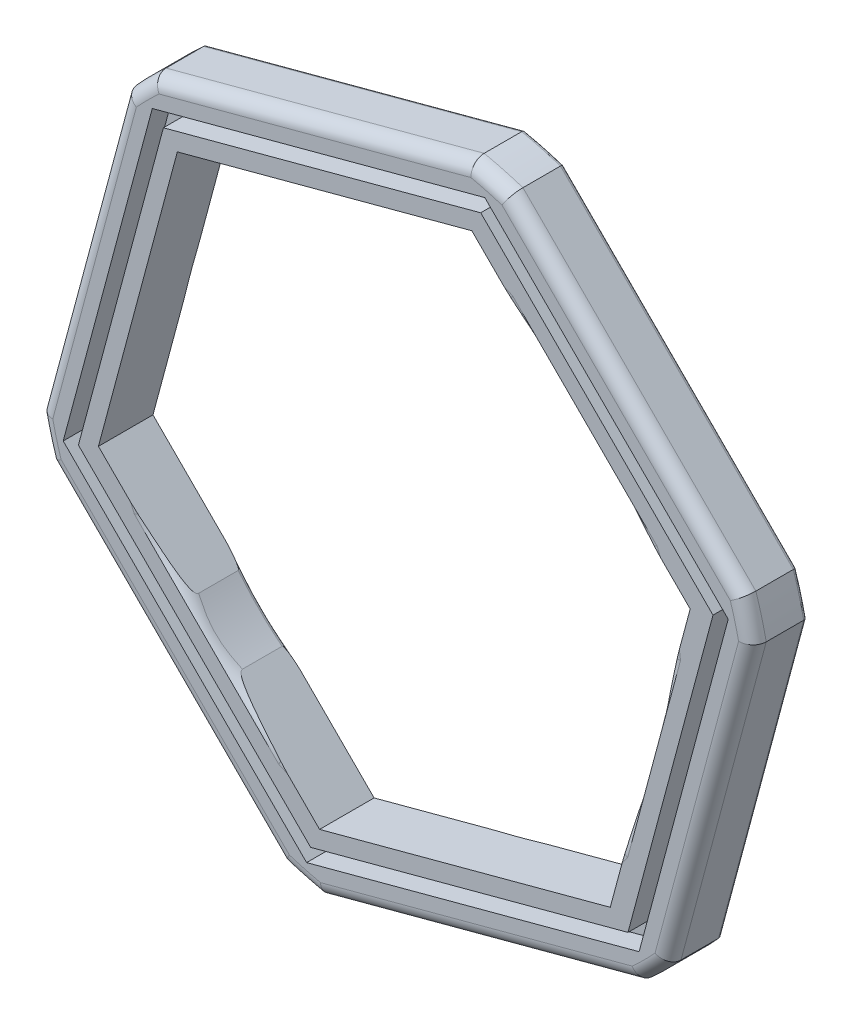
SolidWorks part; units mm, degrees
ref_plane "Спереди" through (0, 0, 0) normal (0, 0, 1) x (1, 0, 0)
ref_plane "Сверху" through (0, 0, 0) normal (0, 1, 0) x (1, 0, 0)
ref_plane "Справа" through (0, 0, 0) normal (1, 0, 0) x (0, 0, -1)
sketch "Эскиз1" plane through (0, 0, 0) normal (0, 0, 1) x (1, 0, 0)
  circle A1 centre (0, 0) radius 53.5
  circle A5 centre (0, 0) radius 39
extrude "Бобышка-Вытянуть1" add sketch "Эскиз1" along normal blind 65
sketch "Эскиз2" plane through (0, 0, 65) normal (0, 0, 1) x (1, 0, 0)
  line L0 (0, 0) -> (-8, 8) construction
  line L1 (-8, 8) -> (-59.1146, 59.1146) construction
  line L2 (-34.0759, 34.0759) -> (-46.5485, -12.4726)
  line L3 (-35.7089, 35.7089) -> (-48.7793, -13.0704)
  line L4 (-48.7793, -13.0704) -> (-13.0704, -48.7793)
  line L5 (-13.0704, -48.7793) -> (35.7089, -35.7089)
  line L6 (35.7089, -35.7089) -> (48.7793, 13.0704)
  line L7 (48.7793, 13.0704) -> (13.0704, 48.7793)
  line L8 (13.0704, 48.7793) -> (-35.7089, 35.7089)
  line L9 (-46.5485, -12.4726) -> (-12.4726, -46.5485)
  line L10 (-12.4726, -46.5485) -> (34.0759, -34.0759)
  line L11 (34.0759, -34.0759) -> (46.5485, 12.4726)
  line L12 (46.5485, 12.4726) -> (12.4726, 46.5485)
  line L13 (12.4726, 46.5485) -> (-34.0759, 34.0759)
  circle A0 centre (0, 0) radius 43.7343 construction
  dimension "D1" = 101
  dimension "D2" = 2
extrude "Вырез-Вытянуть1" cut sketch "Эскиз2" against normal blind 3
sketch "Эскиз3" plane through (0, 0, 65) normal (0, 0, 1) x (1, 0, 0)
  line L0 (43.7602, 11.7255) -> (11.7255, 43.7602)
  line L1 (11.7255, 43.7602) -> (-32.0347, 32.0347)
  line L2 (-32.0347, 32.0347) -> (-43.7602, -11.7255)
  line L3 (-43.7602, -11.7255) -> (-11.7255, -43.7602)
  line L4 (-11.7255, -43.7602) -> (32.0347, -32.0347)
  line L5 (32.0347, -32.0347) -> (43.7602, 11.7255)
  line L6 (46.5485, 12.4726) -> (12.4726, 46.5485)
  line L7 (12.4726, 46.5485) -> (-34.0759, 34.0759)
  line L8 (-34.0759, 34.0759) -> (-46.5485, -12.4726)
  line L9 (-46.5485, -12.4726) -> (-12.4726, -46.5485)
  line L10 (-12.4726, -46.5485) -> (34.0759, -34.0759)
  line L11 (34.0759, -34.0759) -> (46.5485, 12.4726)
  line L12 (46.5485, 12.4726) -> (12.4726, 46.5485)
  line L13 (12.4726, 46.5485) -> (-34.0759, 34.0759)
  line L14 (-34.0759, 34.0759) -> (-46.5485, -12.4726)
  line L15 (-46.5485, -12.4726) -> (-12.4726, -46.5485)
  line L16 (-12.4726, -46.5485) -> (34.0759, -34.0759)
  line L17 (34.0759, -34.0759) -> (46.5485, 12.4726)
  dimension "D1" = 0
  dimension "D2" = 2.5
extrude "Бобышка-Вытянуть2" add sketch "Эскиз3" along normal blind 3
fillet "Скругление2" radius 3 1 edges at (39, 0, 65)
sketch "Эскиз4" plane through (0, 0, 65) normal (0, 0, 1) x (1, 0, 0)
  line L12 (14.2658, 53.2407) -> (-38.9749, 38.9749)
  line L13 (53.2407, 14.2658) -> (14.2658, 53.2407)
  line L14 (38.9749, -38.9749) -> (53.2407, 14.2658)
  line L15 (-14.2658, -53.2407) -> (38.9749, -38.9749)
  line L16 (-53.2407, -14.2658) -> (-14.2658, -53.2407)
  line L17 (-38.9749, 38.9749) -> (-53.2407, -14.2658)
  line L18 (14.2658, 53.2407) -> (-38.9749, 38.9749)
  line L19 (53.2407, 14.2658) -> (14.2658, 53.2407)
  line L20 (38.9749, -38.9749) -> (53.2407, 14.2658)
  line L21 (-14.2658, -53.2407) -> (38.9749, -38.9749)
  line L22 (-53.2407, -14.2658) -> (-14.2658, -53.2407)
  line L23 (-38.9749, 38.9749) -> (-53.2407, -14.2658)
  circle A2 centre (0, 0) radius 58.5
  circle A3 centre (0, 0) radius 58.5
  dimension "D1" = 4
  dimension "D2" = 5
extrude "Вырез-Вытянуть2" cut sketch "Эскиз4" against normal blind 105 contours L18 L23 L22 L21 L20 L19 | A3
fillet "Скругление3" radius 2 12 edges at (13.8468, 51.677, 65) (-12.3545, 46.1078, 65) (-37.8302, 37.8302, 65) (-46.1078, 12.3545, 65) (-51.677, -13.8468, 65) (-33.7532, -33.7532, 65) (-13.8468, -51.677, 65) (37.8302, -37.8302, 65) (12.3545, -46.1078, 65) (33.7532, 33.7532, 65) (51.677, 13.8468, 65) (46.1078, -12.3545, 65)
sketch "Эскиз5" plane through (0, 0, 65) normal (0, 0, 1) x (1, 0, 0)
  line L2 (-11.7255, -43.7602) -> (-4.3237, -41.7769)
  line L3 (-17.144, -38.3417) -> (-11.7255, -43.7602)
  line L4 (-11.7255, -43.7602) -> (-4.3237, -41.7769)
  line L5 (-17.144, -38.3417) -> (-11.7255, -43.7602)
  line L6 (-43.7602, -11.7255) -> (-38.3417, -17.144)
  line L7 (-41.7769, -4.3237) -> (-43.7602, -11.7255)
  line L8 (-43.7602, -11.7255) -> (-38.3417, -17.144)
  line L9 (-41.7769, -4.3237) -> (-43.7602, -11.7255)
  line L10 (-32.0347, 32.0347) -> (-34.018, 24.6329)
  line L11 (-24.6329, 34.018) -> (-32.0347, 32.0347)
  line L12 (-32.0347, 32.0347) -> (-34.018, 24.6329)
  line L13 (-24.6329, 34.018) -> (-32.0347, 32.0347)
  line L14 (11.7255, 43.7602) -> (4.3237, 41.7769)
  line L15 (17.144, 38.3417) -> (11.7255, 43.7602)
  line L16 (11.7255, 43.7602) -> (4.3237, 41.7769)
  line L17 (17.144, 38.3417) -> (11.7255, 43.7602)
  line L18 (43.7602, 11.7255) -> (38.3417, 17.144)
  line L19 (41.7769, 4.3237) -> (43.7602, 11.7255)
  line L20 (43.7602, 11.7255) -> (38.3417, 17.144)
  line L21 (41.7769, 4.3237) -> (43.7602, 11.7255)
  line L22 (32.0347, -32.0347) -> (34.018, -24.6329)
  line L23 (24.6329, -34.018) -> (32.0347, -32.0347)
  line L24 (32.0347, -32.0347) -> (34.018, -24.6329)
  line L25 (24.6329, -34.018) -> (32.0347, -32.0347)
  arc A1 (-17.144, -38.3417) -> (-4.3237, -41.7769) centre (0, 0) ccw
  arc A2 (-17.144, -38.3417) -> (-4.3237, -41.7769) centre (0, 0) ccw
  arc A3 (-41.7769, -4.3237) -> (-38.3417, -17.144) centre (0, 0) ccw
  arc A4 (-41.7769, -4.3237) -> (-38.3417, -17.144) centre (0, 0) ccw
  arc A5 (-24.6329, 34.018) -> (-34.018, 24.6329) centre (0, 0) ccw
  arc A6 (-24.6329, 34.018) -> (-34.018, 24.6329) centre (0, 0) ccw
  arc A7 (17.144, 38.3417) -> (4.3237, 41.7769) centre (0, 0) ccw
  arc A8 (17.144, 38.3417) -> (4.3237, 41.7769) centre (0, 0) ccw
  arc A9 (41.7769, 4.3237) -> (38.3417, 17.144) centre (0, 0) ccw
  arc A10 (41.7769, 4.3237) -> (38.3417, 17.144) centre (0, 0) ccw
  arc A11 (24.6329, -34.018) -> (34.018, -24.6329) centre (0, 0) ccw
  arc A12 (24.6329, -34.018) -> (34.018, -24.6329) centre (0, 0) ccw
  dimension "D1" = 0
  dimension "D2" = 0
  dimension "D3" = 0
  dimension "D4" = 0
  dimension "D5" = 0
  dimension "D6" = 0
extrude "Бобышка-Вытянуть3" add sketch "Эскиз5" along normal blind 3
sketch "Эскиз6" plane through (0, 0, 0) normal (0, 0, -1) x (-1, 0, 0)
  circle A0 centre (-11.841, 44.1911) radius 1.25 construction
  circle A1 centre (32.3501, 32.3501) radius 1.25 construction
  circle A2 centre (44.1911, -11.841) radius 1.25 construction
  circle A3 centre (11.841, -44.1911) radius 1.25 construction
  circle A4 centre (-32.3501, -32.3501) radius 1.25 construction
  circle A5 centre (-44.1911, 11.841) radius 1.25 construction
  circle A6 centre (-11.841, 44.1911) radius 1.25
  circle A7 centre (32.3501, 32.3501) radius 1.25
  circle A8 centre (44.1911, -11.841) radius 1.25
  circle A9 centre (11.841, -44.1911) radius 1.25
  circle A10 centre (-32.3501, -32.3501) radius 1.25
  circle A11 centre (-44.1911, 11.841) radius 1.25
extrude "Вырез-Вытянуть3" cut sketch "Эскиз6" against normal blind 15
sketch "Эскиз7" plane through (-12.3545, 46.1078, 0) normal (-0.2588, 0.9659, 0) x (0.9659, 0.2588, 0)
  line L3 (0, 0) -> (0, -5) construction
  line L4 (0, -5) -> (0, -78.0432) construction
  circle A0 centre (0, -17) radius 8
  point P2 (0, -5)
  point P6 (0, -17)
  dimension "D2" = 16
  dimension "D1" = 12
extrude "Вырез-Вытянуть4" cut sketch "Эскиз7" against normal blind 10 contours A0
sketch "Эскиз9" plane through (-12.3545, 46.1078, 0) normal (-0.2588, 0.9659, 0) x (0.9659, 0.2588, 0)
  circle A2 centre (0, -17) radius 6
  dimension "D1" = 12
extrude "Вытянуть-Тонкостенный1" add sketch "Эскиз9" against normal blind 6 thin thin type one direction wall 3
sketch "Эскиз10" plane through (-12.3545, 46.1078, 0) normal (-0.2588, 0.9659, 0) x (0.9659, 0.2588, 0)
  circle A2 centre (0, -17) radius 8.5
  dimension "D1" = 17
extrude "Вырез-Вытянуть5" cut sketch "Эскиз10" against normal blind 2
sketch "Эскиз11" plane through (0, 0, 0) normal (0, 0, -1) x (-1, 0, 0)
  line L7 (-16.6698, 50.8367) -> (-50.8367, 16.6698)
  line L8 (-52.3608, 10.9819) -> (-39.8548, -35.691)
  line L9 (-35.691, -39.8548) -> (10.9819, -52.3608)
  line L10 (16.6698, -50.8367) -> (50.8367, -16.6698)
  line L11 (52.3608, -10.9819) -> (39.8548, 35.691)
  line L12 (35.691, 39.8548) -> (-10.9819, 52.3608)
  line L13 (-16.6698, 50.8367) -> (-50.8367, 16.6698)
  line L14 (-52.3608, 10.9819) -> (-39.8548, -35.691)
  line L15 (-35.691, -39.8548) -> (10.9819, -52.3608)
  line L16 (16.6698, -50.8367) -> (50.8367, -16.6698)
  line L17 (52.3608, -10.9819) -> (39.8548, 35.691)
  line L18 (35.691, 39.8548) -> (-10.9819, 52.3608)
  arc A7 (-50.8367, 16.6698) -> (-52.3608, 10.9819) centre (0, 0) ccw
  arc A8 (-39.8548, -35.691) -> (-35.691, -39.8548) centre (0, 0) ccw
  arc A9 (10.9819, -52.3608) -> (16.6698, -50.8367) centre (0, 0) ccw
  arc A10 (50.8367, -16.6698) -> (52.3608, -10.9819) centre (0, 0) ccw
  arc A11 (39.8548, 35.691) -> (35.691, 39.8548) centre (0, 0) ccw
  arc A12 (-10.9819, 52.3608) -> (-16.6698, 50.8367) centre (0, 0) ccw
  arc A13 (-50.8367, 16.6698) -> (-52.3608, 10.9819) centre (0, 0) ccw
  arc A14 (-39.8548, -35.691) -> (-35.691, -39.8548) centre (0, 0) ccw
  arc A15 (10.9819, -52.3608) -> (16.6698, -50.8367) centre (0, 0) ccw
  arc A16 (50.8367, -16.6698) -> (52.3608, -10.9819) centre (0, 0) ccw
  arc A17 (39.8548, 35.691) -> (35.691, 39.8548) centre (0, 0) ccw
  arc A18 (-10.9819, 52.3608) -> (-16.6698, 50.8367) centre (0, 0) ccw
  dimension "D1" = 0
extrude "Вырез-Вытянуть6" cut sketch "Эскиз11" against normal blind 50
sketch "Эскиз13" plane through (0, 0, 50) normal (0, 0, -1) x (-1, 0, 0)
  line L0 (35.7089, 35.7089) -> (48.7793, -13.0704) construction
  line L1 (48.7793, -13.0704) -> (13.0704, -48.7793) construction
  line L2 (13.0704, -48.7793) -> (-35.7089, -35.7089) construction
  line L3 (-35.7089, -35.7089) -> (-48.7793, 13.0704) construction
  line L4 (-13.0704, 48.7793) -> (35.7089, 35.7089) construction
  line L5 (-48.7793, 13.0704) -> (-13.0704, 48.7793) construction
  line L6 (35.7089, 35.7089) -> (48.7793, -13.0704)
  line L7 (48.7793, -13.0704) -> (13.0704, -48.7793)
  line L8 (13.0704, -48.7793) -> (-35.7089, -35.7089)
  line L9 (-35.7089, -35.7089) -> (-48.7793, 13.0704)
  line L10 (-13.0704, 48.7793) -> (35.7089, 35.7089)
  line L11 (-48.7793, 13.0704) -> (-13.0704, 48.7793)
  line L24 (45.4332, -12.1738) -> (33.2594, 33.2594)
  line L25 (12.1738, -45.4332) -> (45.4332, -12.1738)
  line L26 (-33.2594, -33.2594) -> (12.1738, -45.4332)
  line L27 (-45.4332, 12.1738) -> (-33.2594, -33.2594)
  line L28 (-12.1738, 45.4332) -> (-45.4332, 12.1738)
  line L29 (33.2594, 33.2594) -> (-12.1738, 45.4332)
  line L30 (45.4332, -12.1738) -> (33.2594, 33.2594)
  line L31 (12.1738, -45.4332) -> (45.4332, -12.1738)
  line L32 (-33.2594, -33.2594) -> (12.1738, -45.4332)
  line L33 (-45.4332, 12.1738) -> (-33.2594, -33.2594)
  line L34 (-12.1738, 45.4332) -> (-45.4332, 12.1738)
  line L35 (33.2594, 33.2594) -> (-12.1738, 45.4332)
  dimension "D1" = 1
extrude "Вырез-Вытянуть7" cut sketch "Эскиз13" against normal blind 6
fillet "Скругление4" radius 1 1 edges at (-39, 0, 50)
fillet "Скругление5" radius 0.5 6 edges at (-42.2441, 11.3193, 56) (-30.9248, -30.9248, 50) (11.3193, -42.2441, 50) (42.2441, -11.3193, 50) (30.9248, 30.9248, 50) (-11.3193, 42.2441, 50)
fillet "Скругление6" radius 0.5 6 edges at (39.3463, -10.5428, 50) (10.5428, -39.3463, 56) (-28.8035, -28.8035, 50) (-39.3463, 10.5428, 56) (-10.5428, 39.3463, 56) (28.8035, 28.8035, 50)
sketch "Эскиз14" plane through (0, 0, 65) normal (0, 0, 1) x (1, 0, 0)
  line L0 (-38.0477, 34.7076) -> (-50.3041, -11.0338) construction
  line L1 (11.0338, 50.3041) -> (-34.7076, 38.0477) construction
  line L2 (49.0816, 15.5965) -> (15.5965, 49.0816) construction
  line L3 (38.0477, -34.7076) -> (50.3041, 11.0338) construction
  line L4 (-49.0816, -15.5965) -> (-15.5965, -49.0816) construction
  line L5 (-11.0338, -50.3041) -> (34.7076, -38.0477) construction
  line L6 (-38.0477, 34.7076) -> (-50.3041, -11.0338)
  line L7 (11.0338, 50.3041) -> (-34.7076, 38.0477)
  line L8 (49.0816, 15.5965) -> (15.5965, 49.0816)
  line L9 (38.0477, -34.7076) -> (50.3041, 11.0338)
  line L10 (-49.0816, -15.5965) -> (-15.5965, -49.0816)
  line L11 (-11.0338, -50.3041) -> (34.7076, -38.0477)
  arc A0 (-50.3041, -11.0338) -> (-49.0816, -15.5965) centre (0, 0) ccw construction
  arc A1 (-34.7076, 38.0477) -> (-38.0477, 34.7076) centre (0, 0) ccw construction
  arc A2 (15.5965, 49.0816) -> (11.0338, 50.3041) centre (0, 0) ccw construction
  arc A3 (50.3041, 11.0338) -> (49.0816, 15.5965) centre (0, 0) ccw construction
  arc A4 (34.7076, -38.0477) -> (38.0477, -34.7076) centre (0, 0) ccw construction
  arc A5 (-15.5965, -49.0816) -> (-11.0338, -50.3041) centre (0, 0) ccw construction
  arc A6 (-50.3041, -11.0338) -> (-49.0816, -15.5965) centre (0, 0) ccw
  arc A7 (-34.7076, 38.0477) -> (-38.0477, 34.7076) centre (0, 0) ccw
  arc A8 (15.5965, 49.0816) -> (11.0338, 50.3041) centre (0, 0) ccw
  arc A9 (50.3041, 11.0338) -> (49.0816, 15.5965) centre (0, 0) ccw
  arc A10 (34.7076, -38.0477) -> (38.0477, -34.7076) centre (0, 0) ccw
  arc A11 (-15.5965, -49.0816) -> (-11.0338, -50.3041) centre (0, 0) ccw
extrude "Вырез-Вытянуть8" cut sketch "Эскиз14" along normal blind 5
sketch "Эскиз16" plane through (0, 0, 50) normal (0, 0, -1) x (-1, 0, 0)
  line L6 (-16.6698, 50.8367) -> (-50.8367, 16.6698)
  line L7 (-52.3608, 10.9819) -> (-39.8548, -35.691)
  line L8 (-35.691, -39.8548) -> (10.9819, -52.3608)
  line L9 (16.6698, -50.8367) -> (50.8367, -16.6698)
  line L10 (52.3608, -10.9819) -> (39.8548, 35.691)
  line L11 (35.691, 39.8548) -> (-10.9819, 52.3608)
  line L12 (-16.6698, 50.8367) -> (-50.8367, 16.6698)
  line L13 (-52.3608, 10.9819) -> (-39.8548, -35.691)
  line L14 (-35.691, -39.8548) -> (10.9819, -52.3608)
  line L15 (16.6698, -50.8367) -> (50.8367, -16.6698)
  line L16 (52.3608, -10.9819) -> (39.8548, 35.691)
  line L17 (35.691, 39.8548) -> (-10.9819, 52.3608)
  arc A6 (-10.9819, 52.3608) -> (-16.6698, 50.8367) centre (0, 0) ccw
  arc A7 (-50.8367, 16.6698) -> (-52.3608, 10.9819) centre (0, 0) ccw
  arc A8 (-39.8548, -35.691) -> (-35.691, -39.8548) centre (0, 0) ccw
  arc A9 (10.9819, -52.3608) -> (16.6698, -50.8367) centre (0, 0) ccw
  arc A10 (50.8367, -16.6698) -> (52.3608, -10.9819) centre (0, 0) ccw
  arc A11 (39.8548, 35.691) -> (35.691, 39.8548) centre (0, 0) ccw
  arc A12 (-10.9819, 52.3608) -> (-16.6698, 50.8367) centre (0, 0) ccw
  arc A13 (-50.8367, 16.6698) -> (-52.3608, 10.9819) centre (0, 0) ccw
  arc A14 (-39.8548, -35.691) -> (-35.691, -39.8548) centre (0, 0) ccw
  arc A15 (10.9819, -52.3608) -> (16.6698, -50.8367) centre (0, 0) ccw
  arc A16 (50.8367, -16.6698) -> (52.3608, -10.9819) centre (0, 0) ccw
  arc A17 (39.8548, 35.691) -> (35.691, 39.8548) centre (0, 0) ccw
  dimension "D1" = 0
extrude "Вырез-Вытянуть9" cut sketch "Эскиз16" against normal blind 5
sketch "Эскиз23" plane through (0, 0, 56) normal (0, 0, -1) x (-1, 0, 0)
  line L0 (13.0704, -48.7793) -> (48.371, -13.4786) construction
  line L1 (45.4332, -12.1738) -> (12.1738, -45.4332) construction
  line L2 (12.1738, -45.4332) -> (-33.2594, -33.2594) construction
  line L3 (-33.2594, -33.2594) -> (-45.4332, 12.1738) construction
  line L4 (-35.7089, -35.7089) -> (-48.7793, 13.0704) construction
  line L5 (-35.7089, -35.7089) -> (13.0704, -48.7793) construction
  line L6 (13.0704, -48.7793) -> (48.371, -13.4786)
  line L7 (45.4332, -12.1738) -> (12.1738, -45.4332)
  line L8 (12.1738, -45.4332) -> (-33.2594, -33.2594)
  line L9 (-33.2594, -33.2594) -> (-45.4332, 12.1738)
  line L10 (-35.7089, -35.7089) -> (-48.7793, 13.0704)
  line L11 (-35.7089, -35.7089) -> (13.0704, -48.7793)
  line L12 (-45.4332, 12.1738) -> (-12.1738, 45.4332) construction
  line L13 (-48.7793, 13.0704) -> (-13.0704, 48.7793) construction
  line L14 (-45.4332, 12.1738) -> (-12.1738, 45.4332)
  line L15 (-48.7793, 13.0704) -> (-13.0704, 48.7793)
  line L16 (33.2594, 33.2594) -> (-12.1738, 45.4332) construction
  line L17 (-13.0704, 48.7793) -> (35.7089, 35.7089) construction
  line L18 (33.2594, 33.2594) -> (-12.1738, 45.4332)
  line L19 (-13.0704, 48.7793) -> (35.7089, 35.7089)
  line L20 (33.2594, 33.2594) -> (45.4332, -12.1738) construction
  line L21 (35.7089, 35.7089) -> (48.7793, -13.0704) construction
  line L22 (33.2594, 33.2594) -> (45.4332, -12.1738)
  line L23 (35.7089, 35.7089) -> (48.7793, -13.0704)
  line M7 (45.8414, -11.7655) -> (11.7655, -45.8414)
  line M8 (11.7655, -45.8414) -> (-33.11, -33.8171)
  line M9 (-33.11, -33.8171) -> (-45.4332, 12.1738)
  line M10 (-45.4332, 12.1738) -> (-11.7655, 45.8414)
  line M11 (-11.7655, 45.8414) -> (33.6677, 33.6677)
  line M12 (33.6677, 33.6677) -> (45.8414, -11.7655)
  line M13 (13.0704, -48.7793) -> (48.371, -13.4786)
  line M14 (48.371, -13.4786) -> (35.1512, 35.8583)
  line M15 (35.1512, 35.8583) -> (-13.0704, 48.7793)
  line M16 (-13.0704, 48.7793) -> (-48.7793, 13.0704)
  line M17 (-48.7793, 13.0704) -> (-35.7089, -35.7089)
  line M18 (-35.7089, -35.7089) -> (13.0704, -48.7793)
extrude "Вырез-Вытянуть11" cut sketch "Эскиз23" against normal blind 4 contours M18 M13 M14 M15 M16 M17 M12 M7 M8 M9 M10 M11 region at (10.9629, -40.9142, 56)
sketch "Эскиз25" plane through (0, 0, 55) normal (0, 0, -1) x (-1, 0, 0)
  line L0 (-35.691, -39.8548) -> (10.9819, -52.3608) construction
  line L1 (16.6698, -50.8367) -> (50.8367, -16.6698) construction
  line L2 (52.3608, -10.9819) -> (39.8548, 35.691) construction
  line L3 (35.691, 39.8548) -> (-10.9819, 52.3608) construction
  line L4 (-16.6698, 50.8367) -> (-50.8367, 16.6698) construction
  line L5 (-52.3608, 10.9819) -> (-39.8548, -35.691) construction
  line L6 (-35.691, -39.8548) -> (10.9819, -52.3608)
  line L7 (16.6698, -50.8367) -> (50.8367, -16.6698)
  line L8 (52.3608, -10.9819) -> (39.8548, 35.691)
  line L9 (35.691, 39.8548) -> (-10.9819, 52.3608)
  line L10 (-16.6698, 50.8367) -> (-50.8367, 16.6698)
  line L11 (-52.3608, 10.9819) -> (-39.8548, -35.691)
  arc A0 (-39.8548, -35.691) -> (-35.691, -39.8548) centre (0, 0) ccw construction
  arc A1 (10.9819, -52.3608) -> (16.6698, -50.8367) centre (0, 0) ccw construction
  arc A2 (50.8367, -16.6698) -> (52.3608, -10.9819) centre (0, 0) ccw construction
  arc A3 (39.8548, 35.691) -> (35.691, 39.8548) centre (0, 0) ccw construction
  arc A4 (-10.9819, 52.3608) -> (-16.6698, 50.8367) centre (0, 0) ccw construction
  arc A5 (-50.8367, 16.6698) -> (-52.3608, 10.9819) centre (0, 0) ccw construction
  arc A6 (-39.8548, -35.691) -> (-35.691, -39.8548) centre (0, 0) ccw
  arc A7 (10.9819, -52.3608) -> (16.6698, -50.8367) centre (0, 0) ccw
  arc A8 (50.8367, -16.6698) -> (52.3608, -10.9819) centre (0, 0) ccw
  arc A9 (39.8548, 35.691) -> (35.691, 39.8548) centre (0, 0) ccw
  arc A10 (-10.9819, 52.3608) -> (-16.6698, 50.8367) centre (0, 0) ccw
  arc A11 (-50.8367, 16.6698) -> (-52.3608, 10.9819) centre (0, 0) ccw
extrude "Вырез-Вытянуть12" cut sketch "Эскиз25" against normal blind 2
fillet "Скругление7" radius 0.5 19 edges at (-39, 0, 57) (42.2441, -11.3193, 57) (11.3193, -42.2441, 57) (-30.7207, -31.1289, 57) (-41.7611, 11.1899, 57) (-11.0404, 42.3188, 57) (30.9248, 30.9248, 57) (46.1078, -12.3545, 57) (51.677, 13.8468, 57) (33.7532, 33.7532, 57) (13.8468, 51.677, 57) (-12.3545, 46.1078, 57) (-37.8302, 37.8302, 57) (-46.1078, 12.3545, 57) (-51.677, -13.8468, 57) (-33.7532, -33.7532, 57) (-13.8468, -51.677, 57) (12.3545, -46.1078, 57) (37.8302, -37.8302, 57)
sketch "Эскиз27" plane through (0, 0, 57) normal (0, 0, -1) x (-1, 0, 0)
  line L12 (-31.477, -32.1841) -> (11.1678, -43.6107)
  line L13 (11.1678, -43.6107) -> (43.6107, -11.1678)
  line L14 (43.6107, -11.1678) -> (32.0347, 32.0347)
  line L15 (32.0347, 32.0347) -> (-11.1678, 43.6107)
  line L16 (-11.1678, 43.6107) -> (-43.2025, 11.5761)
  line L17 (-43.2025, 11.5761) -> (-31.477, -32.1841)
  line L18 (-31.477, -32.1841) -> (11.1678, -43.6107)
  line L19 (11.1678, -43.6107) -> (43.6107, -11.1678)
  line L20 (43.6107, -11.1678) -> (32.0347, 32.0347)
  line L21 (32.0347, 32.0347) -> (-11.1678, 43.6107)
  line L22 (-11.1678, 43.6107) -> (-43.2025, 11.5761)
  line L23 (-43.2025, 11.5761) -> (-31.477, -32.1841)
  dimension "D1" = 2
extrude "Вырез-Вытянуть13" cut sketch "Эскиз27" against normal blind 9
